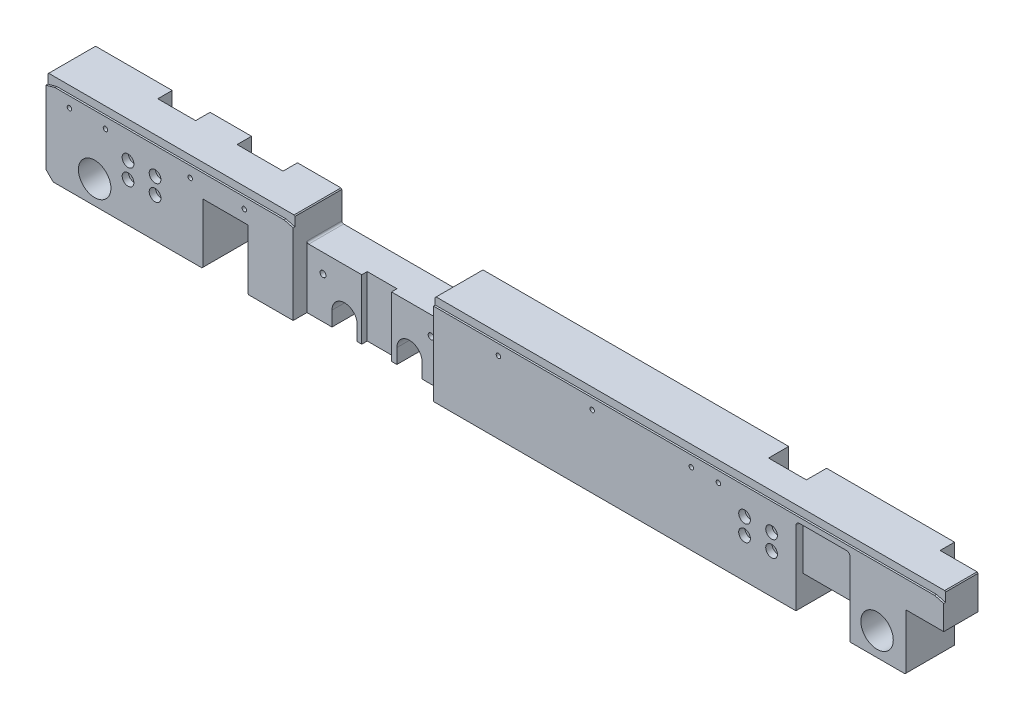
SolidWorks part; units mm, degrees
ref_plane "Front Plane" through (0, 0, 0) normal (0, 0, 1) x (1, 0, 0)
ref_plane "Top Plane" through (0, 0, 0) normal (0, 1, 0) x (1, 0, 0)
ref_plane "Right Plane" through (0, 0, 0) normal (1, 0, 0) x (0, 0, -1)
sketch "Sketch6" plane through (0, 0, 0) normal (0, 0, 1) x (1, 0, 0)
  line L0 (112, -50) -> (477, -50)
  line L1 (0, 0) -> (137.1, 0)
  line L2 (0, 0) -> (0, -50)
  line L3 (0, -50) -> (87, -50)
  line L4 (498, 0) -> (498, -19)
  line L5 (214.9, 0) -> (498, 0)
  line L6 (87, -50) -> (87, -16.6152)
  line L7 (87, -16.6152) -> (112, -16.6152)
  line L8 (112, -50) -> (112, -16.6152)
  line L10 (137.1, 0) -> (137.1, -16.6152)
  line L11 (137.1, -16.6152) -> (214.9, -16.6152)
  line L12 (214.9, 0) -> (214.9, -16.6152)
  line L14 (477, -50) -> (477, -19)
  line L15 (477, -19) -> (498, -19)
  circle A0 centre (27, -37) radius 9
  circle A1 centre (461, -37) radius 9
  point P19 (498, -9.5)
  dimension "D10" = 18
  dimension "D12" = 37
  dimension "D1" = 498
  dimension "D2" = 50
  dimension "D3" = 25
  dimension "D4" = 21
  dimension "D5" = 31
  dimension "D6" = 283.1
  dimension "D7" = 360.9
  dimension "D8" = 386
  dimension "D9" = 471
  dimension "D11" = 13
extrude "Boss-Extrude2" add sketch "Sketch6" along normal blind 27
chamfer "Chamfer1" distance 4 angle 45 1 edges at (0, -50, 13.5)
sketch "Sketch7" plane through (0, 0, 27) normal (0, 0, 1) x (1, 0, 0)
  line L0 (498, -19) -> (498, 0) construction
  line L1 (151, -41.8532) -> (151, -50)
  line L2 (187, -50) -> (201, -50)
  line L3 (187, -41.8532) -> (187, -50)
  line L4 (201, -41.8532) -> (201, -50)
  line L5 (151, -50) -> (165, -50)
  line L6 (112, -50) -> (477, -50) construction
  line L7 (165, -41.8532) -> (165, -50)
  arc A0 (165, -41.8532) -> (151, -41.8532) centre (158, -41.8532) ccw
  arc A1 (201, -41.8532) -> (187, -41.8532) centre (194, -41.8532) ccw
  dimension "D1" = 14
  dimension "D2" = 36
  dimension "D3" = 340
extrude "Cut-Extrude5" cut sketch "Sketch7" against normal through all
chamfer "Chamfer2" distance 0.5 angle 45 2 edges at (214.9, 0, 13.5) (137.1, 0, 13.5)
chamfer "Chamfer3" distance 0.5 angle 45 5 edges at (112, -50, 13.5) (87, -50, 13.5) (0, 0, 13.5) (477, -50, 13.5) (498, 0, 13.5)
sketch "Sketch8" plane through (0, 0, 27) normal (0, 0, 1) x (1, 0, 0)
  line L0 (201, -50) -> (476.5, -50) construction
  line L1 (416, -50) -> (446, -50)
  line L2 (416, -50) -> (416, -7)
  line L3 (416, -7) -> (446, -7)
  line L4 (446, -50) -> (446, -7)
  line L5 (498, -19) -> (498, -0.5) construction
  line L6 (416, -34) -> (446, -34)
  line M11 (201, -50) -> (476.5, -50)
  dimension "D1" = 30
  dimension "D2" = 43
  dimension "D3" = 82
  dimension "D4" = 16
extrude "Cut-Extrude6" cut sketch "Sketch8" against normal blind 27 contours L6 L2 L4 M11 region at (431, -42, 27)
extrude "Cut-Extrude7" cut sketch "Sketch8<3>" against normal blind 4 contours L2 L6 L4 L3 region at (431, -20.5, 27)
sketch "Sketch8<3>" plane through (0, 0, 27) normal (0, 0, 1) x (1, 0, 0) same geometry as "Sketch8"
fillet "Fillet1" radius 2 2 edges at (446, -7, 25) (416, -7, 25)
sketch "Sketch10" plane through (0, 0, 27) normal (0, 0, 1) x (1, 0, 0)
  line L0 (0, -0.5) -> (0, -46) construction
  line L1 (5, -4.1297) -> (132.1, -4.1297)
  line L2 (0, -4.1297) -> (0, 0)
  line L3 (0, 0) -> (498.1127, 0)
  line L4 (498.1127, -4.1297) -> (498.1127, 0)
  line L5 (132.1, -4.1297) -> (137.1, -5.4695)
  line L6 (137.1, -16.6152) -> (137.1, -0.5) construction
  line L7 (137.1, -5.4695) -> (137.1, -4.1297)
  line L8 (0, -4.1297) -> (0, -5.4695)
  line L9 (0, -5.4695) -> (5, -4.1297)
  line L10 (137.1, -4.1297) -> (493, -4.1297)
  line L11 (498.1127, -4.1297) -> (498, -5.4695)
  line L12 (498, -19) -> (498, -0.5) construction
  line L13 (498, -5.4695) -> (493, -4.1297)
  dimension "D1" = 15
  dimension "D2" = 5
  dimension "D3" = 15
  dimension "D4" = 5
  dimension "D5" = 15
  dimension "D6" = 5
extrude "Cut-Extrude8" cut sketch "Sketch10" against normal blind 1
sketch "Sketch11" plane through (0, -50, 0) normal (0, -1, 0) x (1, 0, 0)
  line L0 (498, 27) -> (498, 0) construction
  line L1 (64, -20.6481) -> (43, -20.6481)
  line L2 (64, -20.6481) -> (64, 8)
  line L3 (64, 8) -> (43, 8)
  line L4 (43, -20.6481) -> (43, 8)
  line L5 (4, 0) -> (86.5, 0) construction
  dimension "D1" = 21
  dimension "D2" = 434
  dimension "D3" = 8
extrude "Cut-Extrude9" cut sketch "Sketch11" against normal through all
sketch "Sketch12" plane through (0, -19, 0) normal (0, -1, 0) x (1, 0, 0)
  line L0 (477, 27) -> (477, 0) construction
  line L1 (498, 0) -> (477, 0)
  line L2 (498, 0) -> (498, 8)
  line L3 (498, 8) -> (477, 8)
  line L4 (477, 0) -> (477, 8)
  dimension "D1" = 8
extrude "Cut-Extrude10" cut sketch "Sketch12" against normal through all
sketch "Sketch13" plane through (0, -50, 0) normal (0, -1, 0) x (1, 0, 0)
  line L0 (498, 27) -> (498, 8) construction
  line L1 (385, -19.023) -> (406, -19.023)
  line L2 (385, -19.023) -> (385, 11.1952)
  line L3 (385, 11.1952) -> (406, 11.1952)
  line L4 (406, -19.023) -> (406, 11.1952)
  dimension "D1" = 21
  dimension "D2" = 92
extrude "Cut-Extrude11" cut sketch "Sketch13" against normal through all
sketch "Sketch14" plane through (0, -16.6152, 0) normal (0, 1, 0) x (1, 0, 0)
  line L0 (214.9, -27) -> (214.9, 0) construction
  line L1 (137.1, -27) -> (214.9, -27)
  line L2 (137.1, -27) -> (137.1, -19.35)
  line L3 (137.1, -19.35) -> (167.5, -19.35)
  line L4 (214.9, -27) -> (214.9, -19.35)
  line L5 (214.9, 0) -> (137.1, 0) construction
  line L6 (497.5, -26) -> (497.5, -8) construction
  line L8 (184, -19.35) -> (184, -16.3)
  line L9 (184, -16.3) -> (167.5, -16.3)
  line L10 (167.5, -19.35) -> (167.5, -16.3)
  line L11 (184, -19.35) -> (214.9, -19.35)
  point P13 (167.5, -17.825)
  dimension "D1" = 19.35
  dimension "D2" = 3.05
  dimension "D3" = 330
  dimension "D4" = 30.9
extrude "Cut-Extrude12" cut sketch "Sketch14" against normal through all
sketch "Sketch15" plane through (0, 0, 27) normal (0, 0, 1) x (1, 0, 0)
  line L0 (4, -50) -> (86.5, -50) construction
  line L1 (498, -19) -> (498, -5.4695) construction
  circle A0 centre (45.5, -19) radius 1.75
  circle A1 centre (60.5, -19) radius 1.75
  circle A2 centre (45.5, -28) radius 1.75
  circle A3 centre (60.5, -28) radius 1.75
  circle A4 centre (387.5, -19) radius 1.75
  circle A5 centre (402.5, -19) radius 1.75
  circle A6 centre (387.5, -28) radius 1.75
  circle A7 centre (402.5, -28) radius 1.75
  dimension "D1" = 3.5
  dimension "D3" = 22
  dimension "D4" = 110.5
  dimension "D5" = 95.5
  dimension "D6" = 437.5
  dimension "D7" = 452.5
  dimension "D2" = 31
extrude "Cut-Extrude13" cut sketch "Sketch15" against normal through all
sketch "Sketch16" plane through (0, 0, 27) normal (0, 0, 1) x (1, 0, 0)
  circle A0 centre (45.5, -19) radius 3.25
  circle A1 centre (60.5, -19) radius 3.25
  circle A2 centre (60.5, -28) radius 3.25
  circle A3 centre (45.5, -28) radius 3.25
  circle A4 centre (387.5, -19) radius 3.25
  circle A5 centre (402.5, -19) radius 3.25
  circle A6 centre (402.5, -28) radius 3.25
  circle A7 centre (387.5, -28) radius 3.25
  dimension "D1" = 6.5
extrude "Cut-Extrude14" cut sketch "Sketch16" against normal blind 3.5
fillet "Fillet2" radius 1 2 edges at (214.9, -16.6152, 9.675) (137.1, -16.6152, 9.675)
hole_wizard "M4 Tapped Hole1" positions "Sketch17" profile "Sketch18" tap size "M4" standard "ISO"
sketch "Sketch17" plane through (0, 0, 19.35) normal (0, 0, 1) x (1, 0, 0)
  line L0 (498, -19) -> (498, -5.4695) construction
  line L1 (151, -50) -> (137.1, -50) construction
  line L2 (214.9, -50) -> (201, -50) construction
  point P0 (146, -27)
  point P2 (206, -27)
  dimension "D1" = 352
  dimension "D2" = 292
  dimension "D3" = 23
  dimension "D4" = 23
sketch "Sketch18" plane through (146, -27, 19.35) normal (1, 0, 0) x (0, -1, 0)
  line L0 (0, 0) -> (0, 8.9914)
  line L1 (0, 8.9914) -> (1.65, 8)
  line L2 (1.65, 8) -> (1.65, 0)
  line L5 (1.65, 0) -> (0, 0)
  line L10 (0, 8.9914) -> (-1.65, 8) construction
  line L11 (0, -6.35) -> (0, 107.95) construction
  dimension "Tap Drill Dia." = 3.3
  dimension "Tap Drill Depth" = 8
  dimension "Drill Angle" = 118
cosmetic thread "Hole Thread1" parameters "D1"=8, "D2"=4
cosmetic thread "Hole Thread2" parameters "D1"=8, "D2"=4
hole_wizard "M3 Tapped Hole1" positions "Sketch19" profile "Sketch20" tap size "M3" standard "ISO"
sketch "Sketch19" plane through (0, 0, 27) normal (0, 0, 1) x (1, 0, 0)
  line L0 (498, -19) -> (498, -5.4695) construction
  line L1 (214.9, -50) -> (416, -50) construction
  point P0 (13, -10)
  point P2 (33, -10)
  point P4 (80, -10)
  point P6 (110, -10)
  point P8 (251, -10)
  point P10 (303, -10)
  point P12 (373, -10)
  point P14 (358, -10)
  point P19 (498, -12.2347)
  dimension "D1" = 485
  dimension "D2" = 465
  dimension "D3" = 418
  dimension "D4" = 388
  dimension "D5" = 247
  dimension "D6" = 195
  dimension "D7" = 140
  dimension "D8" = 125
  dimension "D9" = 40
sketch "Sketch20" plane through (13, -10, 27) normal (1, 0, 0) x (0, -1, 0)
  line L0 (0, 0) -> (0, 6.7511)
  line L1 (0, 6.7511) -> (1.25, 6)
  line L2 (1.25, 6) -> (1.25, 0)
  line L5 (1.25, 0) -> (0, 0)
  line L10 (0, 6.7511) -> (-1.25, 6) construction
  line L11 (0, -6.35) -> (0, 107.95) construction
  dimension "Tap Drill Dia." = 2.5
  dimension "Tap Drill Depth" = 6
  dimension "Drill Angle" = 118
cosmetic thread "Hole Thread3" parameters "D1"=6, "D2"=3
cosmetic thread "Hole Thread4" parameters "D1"=6, "D2"=3
cosmetic thread "Hole Thread5" parameters "D1"=6, "D2"=3
cosmetic thread "Hole Thread6" parameters "D1"=6, "D2"=3
cosmetic thread "Hole Thread7" parameters "D1"=6, "D2"=3
cosmetic thread "Hole Thread8" parameters "D1"=6, "D2"=3
cosmetic thread "Hole Thread9" parameters "D1"=6, "D2"=3
cosmetic thread "Hole Thread10" parameters "D1"=6, "D2"=3
hole_wizard "M3 Tapped Hole2" positions "Sketch21" profile "Sketch22" tap size "M3" standard "ISO"
sketch "Sketch21" plane through (0, -19, 0) normal (0, -1, 0) x (-1, 0, 0)
  line L0 (-498, -27) -> (-498, -8) construction
  line L2 (-446, 0) -> (-476.5, 0) construction
  point P0 (-486, -12)
  point P2 (-494, -12)
  dimension "D1" = 4
  dimension "D2" = 12
  dimension "D3" = 12
sketch "Sketch22" plane through (486, -19, 12) normal (1, 0, 0) x (0, 0, -1)
  line L0 (0, 0) -> (0, 6.7511)
  line L1 (0, 6.7511) -> (1.25, 6)
  line L2 (1.25, 6) -> (1.25, 0)
  line L5 (1.25, 0) -> (0, 0)
  line L10 (0, 6.7511) -> (-1.25, 6) construction
  line L11 (0, -6.35) -> (0, 107.95) construction
  dimension "Tap Drill Dia." = 2.5
  dimension "Tap Drill Depth" = 6
  dimension "Drill Angle" = 118
cosmetic thread "Hole Thread11" parameters "D1"=6, "D2"=3
cosmetic thread "Hole Thread12" parameters "D1"=6, "D2"=3
hole_wizard "M3 Tapped Hole3" positions "Sketch23" profile "Sketch24" tap size "M3" standard "ISO"
sketch "Sketch23" plane through (0, -34, 0) normal (0, -1, 0) x (-1, 0, 0)
  line L0 (-498, -27) -> (-498, -8) construction
  line L1 (-416, 0) -> (-446, 0) construction
  point P0 (-424.5, -15.24)
  point P2 (-437.5, -15.24)
  dimension "D1" = 60.5
  dimension "D2" = 73.5
  dimension "D3" = 15.24
sketch "Sketch24" plane through (424.5, -34, 15.24) normal (1, 0, 0) x (0, 0, -1)
  line L0 (0, 0) -> (0, 6.7511)
  line L1 (0, 6.7511) -> (1.25, 6)
  line L2 (1.25, 6) -> (1.25, 0)
  line L5 (1.25, 0) -> (0, 0)
  line L10 (0, 6.7511) -> (-1.25, 6) construction
  line L11 (0, -6.35) -> (0, 107.95) construction
  dimension "Tap Drill Dia." = 2.5
  dimension "Tap Drill Depth" = 6
  dimension "Drill Angle" = 118
cosmetic thread "Hole Thread13" parameters "D1"=6, "D2"=3
cosmetic thread "Hole Thread14" parameters "D1"=6, "D2"=3
hole_wizard "M3 Tapped Hole4" positions "Sketch25" profile "Sketch26" tap size "M3" standard "ISO"
sketch "Sketch25" plane through (0, -50, 0) normal (0, -1, 0) x (-1, 0, 0)
  line L0 (-498, -27) -> (-498, -8) construction
  line L1 (-112.5, 0) -> (-151, 0) construction
  point P0 (-138.7, -12.9)
  point P2 (-146.7, -12.9)
  point P7 (-498, -17.5)
  dimension "D1" = 359.3
  dimension "D2" = 351.3
  dimension "D3" = 12.9
  dimension "D4" = 12.9
sketch "Sketch26" plane through (138.7, -50, 12.9) normal (1, 0, 0) x (0, 0, -1)
  line L0 (0, 0) -> (0, 6.7511)
  line L1 (0, 6.7511) -> (1.25, 6)
  line L2 (1.25, 6) -> (1.25, 0)
  line L5 (1.25, 0) -> (0, 0)
  line L10 (0, 6.7511) -> (-1.25, 6) construction
  line L11 (0, -6.35) -> (0, 107.95) construction
  dimension "Tap Drill Dia." = 2.5
  dimension "Tap Drill Depth" = 6
  dimension "Drill Angle" = 118
cosmetic thread "Hole Thread15" parameters "D1"=6, "D2"=3
cosmetic thread "Hole Thread16" parameters "D1"=6, "D2"=3
hole_wizard "M3 Tapped Hole5" positions "Sketch27" profile "Sketch28" tap size "M3" standard "ISO"
sketch "Sketch27" plane through (0, -16.6152, 0) normal (0, -1, 0) x (-1, 0, 0)
  line L0 (-87, 0) -> (-112, 0) construction
  line L1 (-498, -27) -> (-498, -8) construction
  point P0 (-95.5, -12)
  point P2 (-103.5, -12)
  dimension "D1" = 12
  dimension "D2" = 12
  dimension "D3" = 402.5
  dimension "D4" = 394.5
sketch "Sketch28" plane through (95.5, -16.6152, 12) normal (1, 0, 0) x (0, 0, -1)
  line L0 (0, 0) -> (0, 6.7511)
  line L1 (0, 6.7511) -> (1.25, 6)
  line L2 (1.25, 6) -> (1.25, 0)
  line L5 (1.25, 0) -> (0, 0)
  line L10 (0, 6.7511) -> (-1.25, 6) construction
  line L11 (0, -6.35) -> (0, 107.95) construction
  dimension "Tap Drill Dia." = 2.5
  dimension "Tap Drill Depth" = 6
  dimension "Drill Angle" = 118
cosmetic thread "Hole Thread17" parameters "D1"=6, "D2"=3
cosmetic thread "Hole Thread18" parameters "D1"=6, "D2"=3
sketch "Sketch29" plane through (0, -16.6152, 0) normal (0, -1, 0) x (1, 0, 0)
  line L0 (87, 27) -> (87, 0) construction
  line L1 (112.5, 0) -> (87, 0)
  line L2 (112.5, 0) -> (112.5, 8)
  line L3 (112.5, 8) -> (87, 8)
  line L4 (87, 0) -> (87, 8)
  line L7 (87, 27) -> (112, 27) construction
  dimension "D1" = 19
extrude "Cut-Extrude15" cut sketch "Sketch29" against normal through all
ref_plane "Plane1" through (0, 10, 0) normal (0, 1, 0) x (-1, 0, 0)
